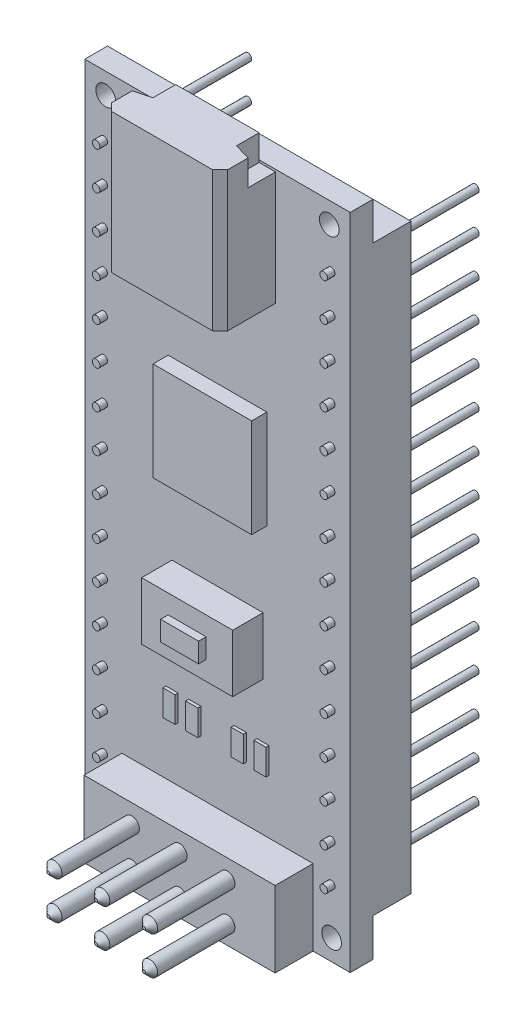
SolidWorks part; units mm, degrees
ref_plane "Plan de face" through (0, 0, 0) normal (0, 0, 1) x (1, 0, 0)
ref_plane "Plan de dessus" through (0, 0, 0) normal (0, 1, 0) x (1, 0, 0)
ref_plane "Plan de droite" through (0, 0, 0) normal (1, 0, 0) x (0, 0, -1)
sketch "Esquisse1" plane through (0, 0, 0) normal (0, 0, 1) x (1, 0, 0)
  line L1 (0, 0) -> (-17.5, 0)
  line L2 (0, 0) -> (0, 43.4)
  line L3 (0, 43.4) -> (-17.5, 43.4)
  line L4 (-17.5, 0) -> (-17.5, 43.4)
  dimension "D1" = 43.4
  dimension "D2" = 17.5
extrude "Boss.-Extru.1" add sketch "Esquisse1" along normal blind 1.5
sketch "Esquisse2" plane through (0, 0, 1.5) normal (0, 0, 1) x (1, 0, 0)
  line L0 (0, 43.4) -> (-17.5, 43.4) construction
  line L1 (-12.575, 51.05) -> (-4.925, 51.05)
  line L2 (-12.575, 51.05) -> (-12.575, 35.75)
  line L3 (-12.575, 35.75) -> (-4.925, 35.75)
  line L4 (-4.925, 51.05) -> (-4.925, 35.75)
  line L5 (-12.575, 51.05) -> (-4.925, 35.75) construction
  line L6 (-12.575, 35.75) -> (-4.925, 51.05) construction
  line L8 (-12.575, 51.05) -> (-4.925, 51.05)
  line L9 (-12.575, 51.05) -> (-12.575, 44.95)
  line L10 (-12.575, 44.95) -> (-4.925, 44.95)
  line L11 (-4.925, 51.05) -> (-4.925, 44.95)
  point P0 (-8.75, 43.4)
  line M6 (0, 43.4) -> (-17.5, 43.4)
  dimension "D1" = 7.65
  dimension "D2" = 15.3
  dimension "D3" = 9.2
extrude "Boss.-Extru.2" add sketch "Esquisse2" along normal blind 3.65 contours L4 L2 L3 M6 | L10 L2 L4 M6 region at (-8.75, 44.175, 1.5) region at (-8.75, 39.575, 1.5)
sketch "Esquisse3" plane through (0, 0, 1.5) normal (0, 0, 1) x (1, 0, 0)
  line L0 (-17.5, 0) -> (0, 0) construction
  line L1 (-15.05, -5) -> (-2.45, -5)
  line L2 (-15.05, -5) -> (-15.05, 5)
  line L3 (-15.05, 5) -> (-2.45, 5)
  line L4 (-2.45, -5) -> (-2.45, 5)
  line L5 (-15.05, -5) -> (-2.45, 5) construction
  line L6 (-15.05, 5) -> (-2.45, -5) construction
  line L7 (-2.45, 0) -> (-15.05, 0)
  point P0 (-8.75, 0)
  line M11 (-17.5, 0) -> (0, 0)
  dimension "D1" = 10
  dimension "D2" = 12.6
extrude "Boss.-Extru.3" add sketch "Esquisse3" along normal blind 2.5 contours L4 L3 L2 M11 region at (-8.75, 2.5, 1.5)
sketch "Esquisse4" plane through (0, 0, 0) normal (0, 0, -1) x (-1, 0, 0)
  line L0 (17.5, 0) -> (0, 0) construction
  line L1 (0, 43.4) -> (2.5, 43.4)
  line L2 (0, 43.4) -> (0, 0)
  line L3 (0, 0) -> (2.5, 0)
  line L4 (2.5, 43.4) -> (2.5, 0)
  line L5 (0, 43.4) -> (17.5, 43.4) construction
  line L6 (17.5, 0) -> (15, 0)
  line L7 (17.5, 0) -> (17.5, 43.4)
  line L8 (17.5, 43.4) -> (15, 43.4)
  line L9 (15, 0) -> (15, 43.4)
  line L11 (0, 43.4) -> (2.5, 43.4)
  line L12 (0, 43.4) -> (0, 40.9)
  line L13 (0, 40.9) -> (2.5, 40.9)
  line L14 (2.5, 43.4) -> (2.5, 40.9)
  line L15 (15, 43.4) -> (17.5, 43.4)
  line L16 (15, 43.4) -> (15, 40.9)
  line L17 (15, 40.9) -> (17.5, 40.9)
  line L18 (17.5, 43.4) -> (17.5, 40.9)
  line L19 (0, 0) -> (2.5, 0)
  line L20 (0, 0) -> (0, 2.5)
  line L21 (0, 2.5) -> (2.5, 2.5)
  line L22 (2.5, 0) -> (2.5, 2.5)
  line L23 (15, 0) -> (17.5, 0)
  line L24 (15, 0) -> (15, 2.5)
  line L25 (15, 2.5) -> (17.5, 2.5)
  line L26 (17.5, 0) -> (17.5, 2.5)
  dimension "D1" = 2.5
  dimension "D2" = 2.5
  dimension "D3" = 2.5
  dimension "D4" = 2.5
  dimension "D5" = 2.5
  dimension "D6" = 2.5
extrude "Boss.-Extru.4" add sketch "Esquisse4" along normal blind 2.5 contours L2 L21 L4 L13 | L9 L25 L7 L17 region at (-1.25, 21.7, 0) region at (-16.25, 21.7, 0)
sketch "Esquisse5" plane through (0, 0, -2.5) normal (0, 0, -1) x (-1, 0, 0)
  line L0 (16.25, 40.9) -> (16.25, 2.5) construction
  line L1 (15, 40.9) -> (17.5, 40.9) construction
  line L2 (15, 2.5) -> (17.5, 2.5) construction
  line L3 (16.25, 40.9) -> (16.25, 39.4) construction
  line L4 (8.75, 43.4) -> (8.75, 0) construction
  line L5 (4.925, 43.4) -> (12.575, 43.4) construction
  line L6 (17.5, 0) -> (0, 0) construction
  circle A0 centre (16.25, 39.4) radius 0.25
  circle A1 centre (16.25, 36.9) radius 0.25
  circle A2 centre (16.25, 34.4) radius 0.25
  circle A3 centre (16.25, 31.9) radius 0.25
  circle A4 centre (16.25, 29.4) radius 0.25
  circle A5 centre (16.25, 26.9) radius 0.25
  circle A6 centre (16.25, 24.4) radius 0.25
  circle A7 centre (16.25, 21.9) radius 0.25
  circle A8 centre (16.25, 19.4) radius 0.25
  circle A9 centre (16.25, 16.9) radius 0.25
  circle A10 centre (16.25, 14.4) radius 0.25
  circle A11 centre (16.25, 11.9) radius 0.25
  circle A12 centre (16.25, 9.4) radius 0.25
  circle A13 centre (16.25, 6.9) radius 0.25
  circle A14 centre (16.25, 4.4) radius 0.25
  circle A15 centre (1.25, 4.4) radius 0.25
  circle A16 centre (1.25, 6.9) radius 0.25
  circle A17 centre (1.25, 9.4) radius 0.25
  circle A18 centre (1.25, 11.9) radius 0.25
  circle A19 centre (1.25, 14.4) radius 0.25
  circle A20 centre (1.25, 16.9) radius 0.25
  circle A21 centre (1.25, 19.4) radius 0.25
  circle A22 centre (1.25, 21.9) radius 0.25
  circle A23 centre (1.25, 24.4) radius 0.25
  circle A24 centre (1.25, 26.9) radius 0.25
  circle A25 centre (1.25, 29.4) radius 0.25
  circle A26 centre (1.25, 31.9) radius 0.25
  circle A27 centre (1.25, 34.4) radius 0.25
  circle A28 centre (1.25, 36.9) radius 0.25
  circle A29 centre (1.25, 39.4) radius 0.25
  dimension "D2" = 0.5
  dimension "D1" = 1.5
  dimension "D3" = 15
extrude "Boss.-Extru.5" add sketch "Esquisse5" along normal blind 5.5 and the other way blind 4.5
sketch "Esquisse6" plane through (0, 0, 1.5) normal (0, 0, 1) x (1, 0, 0)
  line L0 (-8.75, 5) -> (-8.75, 35.75) construction
  line L1 (-15.05, 5) -> (-2.45, 5) construction
  line L2 (-12.575, 35.75) -> (-4.925, 35.75) construction
  line L4 (-12, 29.25) -> (-5.5, 29.25)
  line L5 (-12, 29.25) -> (-12, 22.75)
  line L6 (-12, 22.75) -> (-5.5, 22.75)
  line L7 (-5.5, 29.25) -> (-5.5, 22.75)
  line L8 (-12, 29.25) -> (-5.5, 22.75) construction
  line L9 (-12, 22.75) -> (-5.5, 29.25) construction
  point P6 (-8.75, 26)
  dimension "D1" = 6.5
  dimension "D2" = 6.5
  dimension "D3" = 6.5
extrude "Boss.-Extru.6" add sketch "Esquisse6" along normal blind 1
sketch "Esquisse7" plane through (0, 0, 1.5) normal (0, 0, 1) x (1, 0, 0)
  line L0 (-8.75, 5) -> (-8.75, 22.75) construction
  line L1 (-15.05, 5) -> (-2.45, 5) construction
  line L2 (-12, 22.75) -> (-5.5, 22.75) construction
  line L4 (-5.75, 17.673) -> (-11.75, 17.673)
  line L5 (-5.75, 17.673) -> (-5.75, 13.873)
  line L6 (-5.75, 13.873) -> (-11.75, 13.873)
  line L7 (-11.75, 17.673) -> (-11.75, 13.873)
  line L8 (-5.75, 17.673) -> (-11.75, 13.873) construction
  line L9 (-5.75, 13.873) -> (-11.75, 17.673) construction
  point P6 (-8.75, 15.773)
  dimension "D1" = 3.8
  dimension "D2" = 6
extrude "Boss.-Extru.9" add sketch "Esquisse7" along normal blind 2
sketch "Esquisse8" plane through (0, 0, 3.5) normal (0, 0, 1) x (1, 0, 0)
  line L0 (-8.75, 13.873) -> (-8.75, 17.673) construction
  line L1 (-11.75, 13.873) -> (-5.75, 13.873) construction
  line L2 (-5.75, 17.673) -> (-11.75, 17.673) construction
  line L4 (-7.5, 15.123) -> (-10, 15.123)
  line L5 (-7.5, 15.123) -> (-7.5, 16.423)
  line L6 (-7.5, 16.423) -> (-10, 16.423)
  line L7 (-10, 15.123) -> (-10, 16.423)
  line L8 (-7.5, 15.123) -> (-10, 16.423) construction
  line L9 (-7.5, 16.423) -> (-10, 15.123) construction
  point P6 (-8.75, 15.773)
  dimension "D1" = 2.5
  dimension "D2" = 1.3
extrude "Boss.-Extru.10" add sketch "Esquisse8" along normal blind 0.5
sketch "Esquisse9" plane through (0, 0, 1.5) normal (0, 0, 1) x (1, 0, 0)
  line L0 (-8.75, 5) -> (-8.75, 13.873) construction
  line L1 (-15.05, 5) -> (-2.45, 5) construction
  line L2 (-11.75, 13.873) -> (-5.75, 13.873) construction
  line L3 (-8.75, 9.4365) -> (-5.75, 9.4365) construction
  line L4 (-8.75, 9.4365) -> (-11.75, 9.4365) construction
  line L6 (-6.15, 8.5865) -> (-5.35, 8.5865)
  line L7 (-6.15, 8.5865) -> (-6.15, 10.2865)
  line L8 (-6.15, 10.2865) -> (-5.35, 10.2865)
  line L9 (-5.35, 8.5865) -> (-5.35, 10.2865)
  line L10 (-6.15, 8.5865) -> (-5.35, 10.2865) construction
  line L11 (-6.15, 10.2865) -> (-5.35, 8.5865) construction
  line L12 (-9.85, 8.5865) -> (-10.65, 8.5865)
  line L13 (-9.85, 8.5865) -> (-9.85, 10.2865)
  line L14 (-9.85, 10.2865) -> (-10.65, 10.2865)
  line L15 (-10.65, 8.5865) -> (-10.65, 10.2865)
  line L16 (-9.85, 8.5865) -> (-10.65, 10.2865) construction
  line L17 (-9.85, 10.2865) -> (-10.65, 8.5865) construction
  line L18 (-6.85, 8.5865) -> (-7.65, 8.5865)
  line L19 (-6.85, 8.5865) -> (-6.85, 10.2865)
  line L20 (-6.85, 10.2865) -> (-7.65, 10.2865)
  line L21 (-7.65, 8.5865) -> (-7.65, 10.2865)
  line L22 (-6.85, 8.5865) -> (-7.65, 10.2865) construction
  line L23 (-6.85, 10.2865) -> (-7.65, 8.5865) construction
  line L24 (-12.15, 10.2865) -> (-11.35, 10.2865)
  line L25 (-12.15, 10.2865) -> (-12.15, 8.5865)
  line L26 (-12.15, 8.5865) -> (-11.35, 8.5865)
  line L27 (-11.35, 10.2865) -> (-11.35, 8.5865)
  line L28 (-12.15, 10.2865) -> (-11.35, 8.5865) construction
  line L29 (-12.15, 8.5865) -> (-11.35, 10.2865) construction
  point P8 (-10.25, 9.4365)
  point P18 (-7.25, 9.4365)
  dimension "D1" = 3
  dimension "D2" = 3
  dimension "D3" = 0.8
  dimension "D4" = 0.8
  dimension "D5" = 0.8
  dimension "D6" = 0.8
  dimension "D7" = 1.7
  dimension "D8" = 1.7
  dimension "D9" = 1.7
  dimension "D10" = 1.7
extrude "Boss.-Extru.11" add sketch "Esquisse9" along normal blind 0.2
sketch "Esquisse10" plane through (0, 0, 4) normal (0, 0, 1) x (1, 0, 0)
  line L0 (-2.45, 2.5) -> (-15.05, 2.5) construction
  line L1 (-2.45, 0) -> (-2.45, 5) construction
  line L2 (-15.05, 0) -> (-15.05, 5) construction
  line L3 (-8.75, 2.5) -> (-8.75, 5) construction
  line L4 (-15.05, 5) -> (-2.45, 5) construction
  line L5 (-8.75, 2.5) -> (-8.75, 0) construction
  line L6 (-15.05, 0) -> (-2.45, 0) construction
  line L7 (-8.75, 1.25) -> (-2.45, 1.25) construction
  line L8 (-8.75, 1.25) -> (-15.05, 1.25) construction
  line L9 (-15.05, 0) -> (-15.05, 5) construction
  line L10 (-8.75, 3.75) -> (-15.05, 3.75) construction
  line L11 (-8.75, 3.75) -> (-2.45, 3.75) construction
  circle A0 centre (-5.6, 1.25) radius 0.5
  circle A1 centre (-5.6, 3.75) radius 0.5
  circle A2 centre (-8.75, 3.75) radius 0.5
  circle A3 centre (-11.9, 3.75) radius 0.5
  circle A4 centre (-11.9, 1.25) radius 0.5
  circle A5 centre (-8.75, 1.25) radius 0.5
  dimension "D1" = 1
  dimension "D2" = 1
  dimension "D3" = 1
  dimension "D4" = 1
  dimension "D5" = 1
  dimension "D6" = 1
extrude "Boss.-Extru.12" add sketch "Esquisse10" along normal blind 5.5
chamfer "Chanfrein1" distance 0.4 angle 45 6 edges at (-11.4, 3.75, 9.5) (-11.4, 1.25, 9.5) (-8.25, 1.25, 9.5) (-8.25, 3.75, 9.5) (-5.1, 3.75, 9.5) (-5.1, 1.25, 9.5)
sketch "Esquisse11" plane through (0, 44.95, 0) normal (0, 1, 0) x (1, 0, 0)
  line L0 (-8.75, -1.5) -> (-8.75, -5.15) construction
  line L1 (-12.575, -1.5) -> (-4.925, -1.5) construction
  line L2 (-12.575, -5.15) -> (-4.925, -5.15) construction
  line L3 (-8.75, -1.5) -> (-6, -1.5) construction
  line L4 (-8.75, -1.5) -> (-11.5, -1.5) construction
  line L5 (-6, -1.5) -> (-6, -3)
  line L6 (-11.5, -1.5) -> (-11.5, -3)
  line L7 (-6, -3) -> (-4.925, -3) construction
  line L8 (-4.925, -5.15) -> (-4.925, -1.5) construction
  line L9 (-4.925, -3) -> (-4.925, -3.3) construction
  line L10 (-11.5, -3) -> (-12.575, -3) construction
  line L11 (-12.575, -5.15) -> (-12.575, -1.5) construction
  line L12 (-12.575, -3) -> (-12.575, -3.3) construction
  line L13 (-11.5, -3) -> (-12.575, -3.3)
  line L14 (-4.925, -3.3) -> (-6, -3)
  line L15 (-4.925, -3.3) -> (-4.925, -1.5)
  line L16 (-4.925, -1.5) -> (-6, -1.5)
  line L17 (-11.5, -1.5) -> (-12.575, -1.5)
  line L18 (-12.575, -1.5) -> (-12.575, -3.3)
  dimension "D1" = 2.75
  dimension "D2" = 2.75
  dimension "D3" = 1.5
  dimension "D4" = 1.5
  dimension "D5" = 0.3
  dimension "D6" = 0.3
extrude "Enlèv. mat.-Extru.1" cut sketch "Esquisse11" against normal blind 1.7
chamfer "Chanfrein2" distance 0.5 angle 45 2 edges at (-12.575, 40.35, 5.15) (-4.925, 40.35, 5.15)
sketch "Esquisse12" plane through (0, 0, 1.5) normal (0, 0, 1) x (1, 0, 0)
  line L0 (-15.05, 0) -> (-15.05, 5) construction
  line L1 (-17.5, 0) -> (-15.05, 0)
  line L2 (-17.5, 0) -> (-17.5, 2.76)
  line L3 (-17.5, 2.76) -> (-15.05, 2.76)
  line L4 (-15.05, 0) -> (-15.05, 2.76)
  line L5 (-17.5, 0) -> (-15.05, 2.76) construction
  line L6 (-2.45, 0) -> (-2.45, 5) construction
  line L7 (0, 0) -> (-2.45, 0)
  line L8 (0, 0) -> (0, 2.76)
  line L9 (0, 2.76) -> (-2.45, 2.76)
  line L10 (-2.45, 0) -> (-2.45, 2.76)
  line L11 (0, 0) -> (-2.45, 2.76) construction
  line L12 (-14.74, 40.64) -> (-17.5, 43.4) construction
  line L13 (0, 43.4) -> (-2.76, 43.4)
  line L14 (0, 43.4) -> (0, 40.64)
  line L15 (0, 40.64) -> (-2.76, 40.64)
  line L16 (-2.76, 43.4) -> (-2.76, 40.64)
  line L17 (-17.5, 43.4) -> (-14.74, 43.4)
  line L18 (-17.5, 43.4) -> (-17.5, 40.64)
  line L19 (-17.5, 40.64) -> (-14.74, 40.64)
  line L20 (-14.74, 43.4) -> (-14.74, 40.64)
  line L21 (-2.76, 40.64) -> (0, 43.4) construction
  circle A0 centre (-16.275, 1.38) radius 0.65
  circle A1 centre (-1.225, 1.38) radius 0.65
  circle A2 centre (-16.12, 42.02) radius 0.65
  circle A3 centre (-1.38, 42.02) radius 0.65
  dimension "D2" = 1.3
  dimension "D4" = 1.3
  dimension "D9" = 1.3
  dimension "D10" = 1.3
  dimension "D1" = 2.76
  dimension "D3" = 2.76
  dimension "D5" = 2.76
  dimension "D6" = 2.76
  dimension "D7" = 2.76
  dimension "D8" = 2.76
extrude "Enlèv. mat.-Extru.2" cut sketch "Esquisse12" against normal blind 5.7 contours A3 | A2 | A0 | A1
sketch "Esquisse13" plane through (0, 0, 0) normal (0, 0, -1) x (-1, 0, 0)
  line L0 (0, 43.4) -> (17.5, 43.4) construction
  line L1 (14.5, 6.5) -> (9, 6.5)
  line L2 (14.5, 6.5) -> (14.5, 9.5)
  line L3 (14.5, 9.5) -> (9, 9.5)
  line L4 (9, 6.5) -> (9, 9.5)
  line L5 (9, 25.4) -> (5.5, 25.4)
  line L6 (9, 25.4) -> (9, 35.4)
  line L7 (9, 35.4) -> (5.5, 35.4)
  line L8 (5.5, 25.4) -> (5.5, 35.4)
  line L9 (5.75, 39.4) -> (4.75, 39.4)
  line L10 (5.75, 39.4) -> (5.75, 42.4)
  line L11 (5.75, 42.4) -> (4.75, 42.4)
  line L12 (4.75, 39.4) -> (4.75, 42.4)
  line L13 (7.75, 42.4) -> (6.75, 42.4)
  line L14 (7.75, 42.4) -> (7.75, 39.4)
  line L15 (7.75, 39.4) -> (6.75, 39.4)
  line L16 (6.75, 42.4) -> (6.75, 39.4)
  line L17 (8, 6.5) -> (7, 6.5)
  line L18 (8, 6.5) -> (8, 9.5)
  line L19 (8, 9.5) -> (7, 9.5)
  line L20 (7, 6.5) -> (7, 9.5)
  line L21 (0, 40.9) -> (0, 2.5) construction
  line L22 (17.5, 0) -> (0, 0) construction
  line L23 (17.5, 2.5) -> (17.5, 40.9) construction
  line L24 (17.5, 43.4) -> (17.5, 40.9) construction
  line L25 (11.75, 40.4) -> (10.75, 40.4)
  line L26 (11.75, 40.4) -> (11.75, 42.4)
  line L27 (11.75, 42.4) -> (10.75, 42.4)
  line L28 (10.75, 40.4) -> (10.75, 42.4)
  line L29 (14.75, 40.4) -> (13.75, 40.4)
  line L30 (14.75, 40.4) -> (14.75, 42.4)
  line L31 (14.75, 42.4) -> (13.75, 42.4)
  line L32 (13.75, 40.4) -> (13.75, 42.4)
  line L34 (3.75, 39.4) -> (2.75, 39.4)
  line L35 (3.75, 39.4) -> (3.75, 42.4)
  line L36 (3.75, 42.4) -> (2.75, 42.4)
  line L37 (2.75, 39.4) -> (2.75, 42.4)
  dimension "D1" = 5.5
  dimension "D2" = 3
  dimension "D3" = 1
  dimension "D4" = 3
  dimension "D5" = 3.5
  dimension "D6" = 10
  dimension "D7" = 8
  dimension "D8" = 5.5
  dimension "D9" = 6.5
  dimension "D10" = 6.5
  dimension "D11" = 3
  dimension "D12" = 1
  dimension "D13" = 1
  dimension "D14" = 1
  dimension "D15" = 1
  dimension "D16" = 1
  dimension "D17" = 1
  dimension "D18" = 1
  dimension "D19" = 1
  dimension "D20" = 1
  dimension "D21" = 2
  dimension "D22" = 2
  dimension "D23" = 3
  dimension "D24" = 3
  dimension "D25" = 2.75
  dimension "D26" = 2
  dimension "D27" = 3
  dimension "D28" = 1
  dimension "D29" = 1
  dimension "D30" = 1
extrude "Boss.-Extru.13" add sketch "Esquisse13" along normal blind 1
